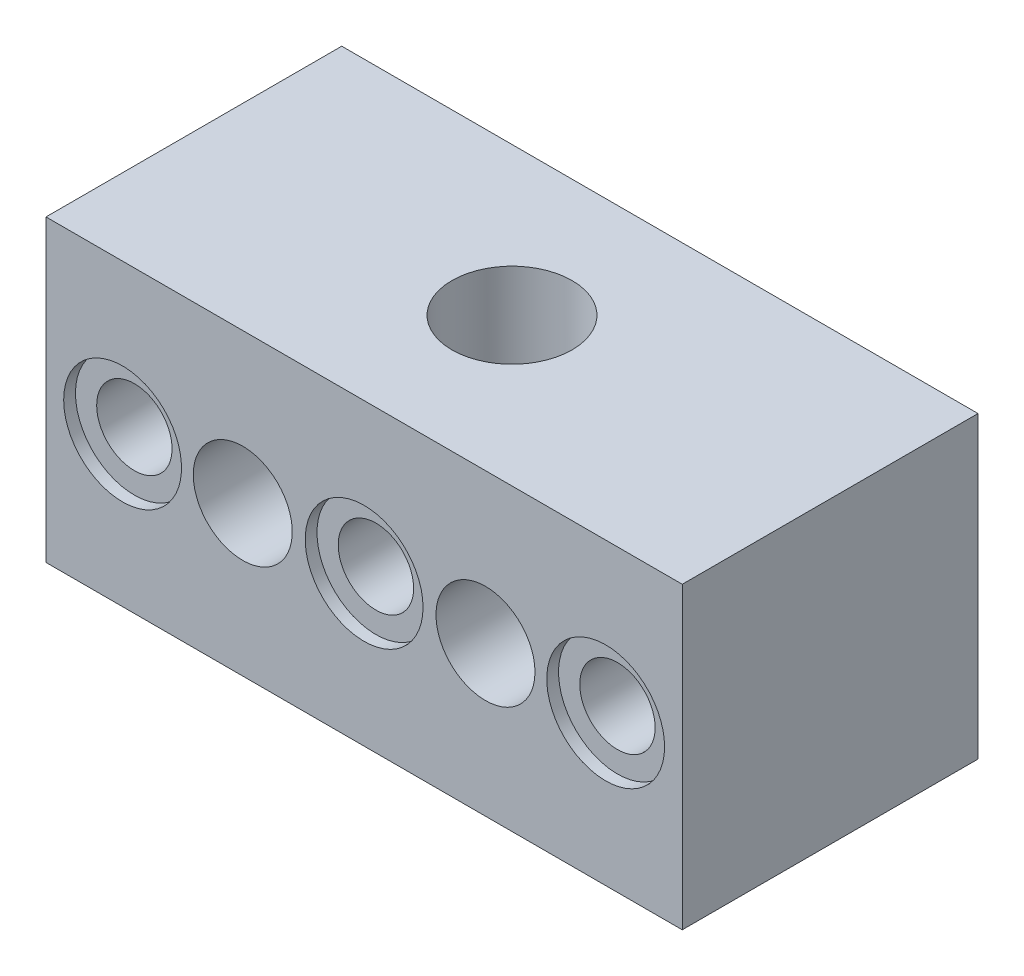
SolidWorks part; units mm, degrees
material "Nickel"
ref_plane "Front Plane" through (0, 0, 0) normal (0, 0, 1) x (1, 0, 0)
ref_plane "Top Plane" through (0, 0, 0) normal (0, 1, 0) x (1, 0, 0)
ref_plane "Right Plane" through (0, 0, 0) normal (1, 0, 0) x (0, 0, -1)
sketch "Sketch1" plane through (0, 0, 0) normal (0, 0, 1) x (1, 0, 0)
  line L1 (27, 12.7) -> (-27, 12.7)
  line L2 (27, 12.7) -> (27, -12.7)
  line L3 (27, -12.7) -> (-27, -12.7)
  line L4 (-27, 12.7) -> (-27, -12.7)
  line L5 (27, 12.7) -> (-27, -12.7) construction
  line L6 (27, -12.7) -> (-27, 12.7) construction
  point P0 (0, 0)
  dimension "D1" = 25.4
  dimension "D2" = 54
extrude "Boss-Extrude1" add sketch "Sketch1" along normal blind 12.55 and the other way blind 12.55
sketch "Sketch3" plane through (0, -12.7, 0) normal (0, -1, 0) x (1, 0, 0)
  circle A0 centre (0, 0) radius 5.1
  dimension "D1" = 10.2
extrude "Cut-Extrude1" cut sketch "Sketch3" against normal up to next
sketch "Sketch5" plane through (0, 0, 12.55) normal (0, 0, 1) x (1, 0, 0)
  line L0 (27, -12.7) -> (27, 12.7) construction
  line L1 (0, 0) -> (0, 12.7) construction
  line L2 (27, 12.7) -> (-27, 12.7) construction
  circle A0 centre (20.5, 0) radius 5
  circle A1 centre (-20.5, 0) radius 5
  dimension "D1" = 10
  dimension "D3" = 20.5
  dimension "D2" = 6.5
extrude "Cut-Extrude2" cut sketch "Sketch5" against normal blind 1
sketch "Sketch6" plane through (0, 0, 11.55) normal (0, 0, 1) x (1, 0, 0)
  line L0 (0, 0) -> (0, 12.7) construction
  line L1 (27, 12.7) -> (-27, 12.7) construction
  circle A0 centre (20.5, 0) radius 3.2
  circle A1 centre (-20.5, 0) radius 3.2
  dimension "D1" = 6.4
extrude "Cut-Extrude3" cut sketch "Sketch6" against normal blind 4.6
sketch "Sketch7" plane through (0, 0, 6.95) normal (0, 0, 1) x (1, 0, 0)
  line L0 (0, 0) -> (0, 12.7) construction
  line L1 (27, 12.7) -> (-27, 12.7) construction
  circle A0 centre (20.5, 0) radius 2
  circle A1 centre (-20.5, 0) radius 2
  dimension "D1" = 4
extrude "Cut-Extrude4" cut sketch "Sketch7" against normal up to next
mirror "Mirror1" about plane through (0, 0, 0) normal (0, 0, 1) of "Cut-Extrude2"
mirror "Mirror2" about plane through (0, 0, 0) normal (0, 0, 1) of "Cut-Extrude3"
sketch "Sketch8" plane through (0, 0, 12.55) normal (0, 0, 1) x (1, 0, 0)
  line L0 (0, 0) -> (0, -12.7) construction
  line L1 (-27, -12.7) -> (27, -12.7) construction
  circle A0 centre (10.3, 0) radius 4.2
  circle A1 centre (20.5, 0) radius 5 construction
  circle A2 centre (-10.3, 0) radius 4.2
  dimension "D1" = 8.4
  dimension "D3" = 10.3
  dimension "D2" = 10.2
extrude "Cut-Extrude5" cut sketch "Sketch8" against normal up to next
sketch "Sketch9" plane through (0, 0, 12.55) normal (0, 0, 1) x (1, 0, 0)
  circle A0 centre (0, 0) radius 5
  dimension "D1" = 10
extrude "Cut-Extrude6" cut sketch "Sketch9" against normal blind 1
sketch "Sketch10" plane through (0, 0, 11.55) normal (0, 0, 1) x (1, 0, 0)
  circle A0 centre (0, 0) radius 3.2
  dimension "D1" = 6.4
extrude "Cut-Extrude7" cut sketch "Sketch10" against normal blind 4.6
sketch "Sketch11" plane through (0, 0, 6.95) normal (0, 0, 1) x (1, 0, 0)
  circle A0 centre (0, 0) radius 2
  dimension "D1" = 4
extrude "Cut-Extrude8" cut sketch "Sketch11" against normal through all
mirror "Mirror3" about plane through (0, 0, 0) normal (0, 0, 1) of "Cut-Extrude7", "Cut-Extrude6"
